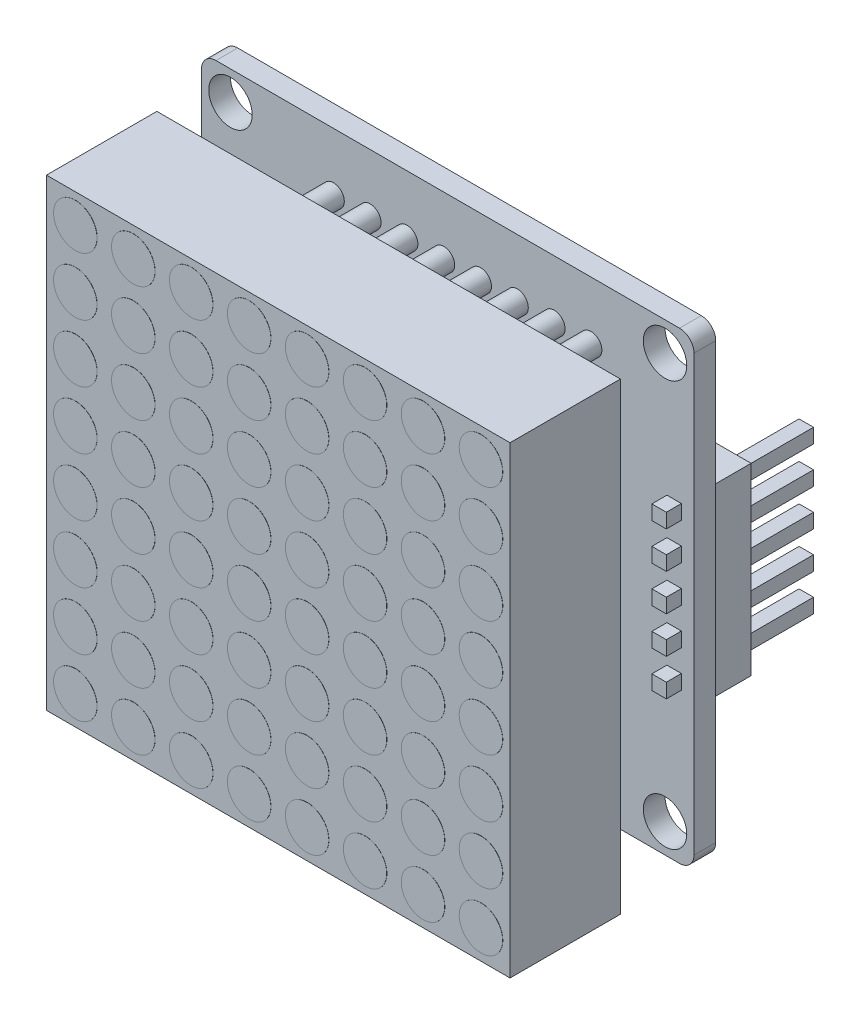
SolidWorks part; units mm, degrees
ref_plane "Alzado" through (0, 0, 0) normal (0, 0, 1) x (1, 0, 0)
ref_plane "Planta" through (0, 0, 0) normal (0, 1, 0) x (1, 0, 0)
ref_plane "Vista lateral" through (0, 0, 0) normal (1, 0, 0) x (0, 0, -1)
sketch "Croquis1" plane through (0, 0, 0) normal (0, 0, 1) x (1, 0, 0)
  line L0 (-22.5, 14) -> (7.5, 14) construction
  line L1 (-23.5, 16) -> (8.5, 16)
  line L2 (-24.5, 15) -> (-24.5, -15)
  line L3 (-23.5, -16) -> (8.5, -16)
  line L4 (9.5, 15) -> (9.5, -15)
  line L7 (-22.5, 14) -> (-22.5, -14) construction
  line L8 (-22.5, -14) -> (7.5, -14) construction
  line L9 (7.5, -14) -> (7.5, 14) construction
  arc A0 (-23.5, -16) -> (-24.5, -15) centre (-23.5, -15) cw
  arc A1 (-23.5, 16) -> (-24.5, 15) centre (-23.5, 15) ccw
  arc A2 (9.5, 15) -> (8.5, 16) centre (8.5, 15) ccw
  arc A3 (9.5, -15) -> (8.5, -16) centre (8.5, -15) cw
  circle A4 centre (-22.5, -14) radius 1.5
  circle A5 centre (-22.5, 14) radius 1.5
  circle A6 centre (7.5, 14) radius 1.5
  circle A7 centre (7.5, -14) radius 1.5
  point P0 (0, 0)
  dimension "D3" = 1
  dimension "D4" = 1
  dimension "D5" = 1
  dimension "D6" = 1
  dimension "D7" = 2
  dimension "D1" = 2
  dimension "D2" = 2
  dimension "D8" = 2
  dimension "D9" = 32
extrude "Saliente-Extruir1" add sketch "Croquis1" along normal blind 1.5
sketch "Croquis2" plane through (0, 0, 1.5) normal (0, 0, 1) x (1, 0, 0)
  line L0 (-24.5, 15) -> (-24.5, -15) construction
  line L1 (-24.4, -6.35) -> (-21.86, -6.35)
  line L2 (-24.4, -6.35) -> (-24.4, 6.35)
  line L3 (-24.4, 6.35) -> (-21.86, 6.35)
  line L4 (-21.86, -6.35) -> (-21.86, 6.35)
  line L5 (-21.86, 0) -> (-24.4, 0) construction
  line L6 (-23.5, -16) -> (8.5, -16) construction
  line L7 (-7.5, 16) -> (-7.5, -16) construction
  line L8 (8.5, 16) -> (-23.5, 16) construction
  line L9 (-24.4, -6.35) -> (-21.86, -6.35)
  line L10 (-24.4, 6.35) -> (-21.86, 6.35)
  line L11 (9.4, 6.35) -> (6.86, 6.35)
  line L12 (6.86, -6.35) -> (6.86, 6.35)
  line L13 (9.4, -6.35) -> (6.86, -6.35)
  line L14 (9.4, -6.35) -> (9.4, 6.35)
  dimension "D1" = 2.54
  dimension "D2" = 12.7
  dimension "D3" = 0.1
  dimension "D4" = 16
extrude "Saliente-Extruir2" add sketch "Croquis2" against normal blind 2.54 from surface contours L1 L4 L3 L2 | L13 L14 L11 L12 region at (-23.13, 0, 1.5) region at (8.13, 0, 1.5) starting at face at (9, 14, 0)
sketch "Croquis3" plane through (0, 0, 1.5) normal (0, 0, 1) x (1, 0, 0)
  line L0 (8.5, 16) -> (-23.5, 16) construction
  line L1 (-22.5, 16) -> (9.5, 16) construction
  line L2 (-22.5, 16) -> (-22.5, -16) construction
  line L3 (-22.5, -16) -> (9.5, -16) construction
  line L4 (9.5, 16) -> (9.5, -16) construction
  line L5 (9.5, -15) -> (9.5, 15) construction
  line L6 (-6.5, 16) -> (-6.5, -16) construction
  line L7 (-16.66, 12) -> (3.66, 12) construction
  line L12 (-16.66, 13.9501) -> (3.66, 13.9501) construction
  line L13 (-16.66, 13.9501) -> (-16.66, 10.0499) construction
  line L14 (-16.66, 10.0499) -> (3.66, 10.0499) construction
  line L15 (3.66, 13.9501) -> (3.66, 10.0499) construction
  line L16 (-22.5, 0) -> (-6.5, 0) construction
  line L17 (-6.5, 13.9501) -> (-6.5, 10.0499) construction
  circle A0 centre (-15.39, 12) radius 0.75
  circle A1 centre (-12.85, 12) radius 0.75
  circle A2 centre (-10.31, 12) radius 0.75
  circle A3 centre (-7.77, 12) radius 0.75
  circle A4 centre (-5.23, 12) radius 0.75
  circle A5 centre (-2.69, 12) radius 0.75
  circle A6 centre (-0.15, 12) radius 0.75
  circle A7 centre (2.39, 12) radius 0.75
  circle A8 centre (2.39, -12) radius 0.75
  circle A9 centre (-0.15, -12) radius 0.75
  circle A10 centre (-2.69, -12) radius 0.75
  circle A11 centre (-5.23, -12) radius 0.75
  circle A12 centre (-7.77, -12) radius 0.75
  circle A13 centre (-10.31, -12) radius 0.75
  circle A14 centre (-12.85, -12) radius 0.75
  circle A15 centre (-15.39, -12) radius 0.75
  dimension "D2" = 8
  dimension "D3" = 4
  dimension "D4" = 1.27
  dimension "D1" = 32
  dimension "D5" = 20.32
extrude "Saliente-Extruir3" add sketch "Croquis3" along normal mid plane 5.08
sketch "Croquis4" plane through (0, 0, 4.04) normal (0, 0, 1) x (1, 0, 0)
  line L0 (-16.66, 12) -> (3.66, 12) construction
  line L1 (-16.66, 13.2) -> (3.66, 13.2)
  line L2 (-16.66, 13.2) -> (-16.66, 10.8)
  line L3 (-16.66, 10.8) -> (3.66, 10.8)
  line L4 (3.66, 13.2) -> (3.66, 10.8)
  line L5 (-6.5, 13.2) -> (-6.5, 10.8) construction
  line L6 (9.5, -15) -> (9.5, 15) construction
  line L7 (8.5, 16) -> (-23.5, 16) construction
  line L8 (-6.5, 12) -> (-6.5, -12) construction
  line L9 (-6.5, 0) -> (18.66, 0) construction
  line L10 (3.66, -13.2) -> (3.66, -10.8)
  line L11 (-16.66, -10.8) -> (3.66, -10.8)
  line L12 (-16.66, -13.2) -> (-16.66, -10.8)
  line L13 (-16.66, -13.2) -> (3.66, -13.2)
  dimension "D1" = 20.32
  dimension "D2" = 2.4
  dimension "D3" = 16
  dimension "D4" = 4
  dimension "D5" = 24
extrude "Saliente-Extruir4" add sketch "Croquis4" along normal blind 2.54
sketch "Croquis5" plane through (0, 0, 6.58) normal (0, 0, 1) x (1, 0, 0)
  line L0 (-16.66, 12) -> (3.66, 12) construction
  line L1 (-16.66, 13.2) -> (-16.66, 10.8) construction
  line L2 (3.66, 10.8) -> (3.66, 13.2) construction
  line L3 (3.66, 12) -> (-6.5, 13.2) construction
  line L4 (3.66, 13.2) -> (-16.66, 13.2) construction
  line L5 (-6.5, 13.2) -> (-6.7835, 10.8) construction
  line L6 (-16.66, 10.8) -> (3.66, 10.8) construction
  line L7 (-16.66, 12) -> (-16.66, -12) construction
  line L8 (-16.66, -10.8) -> (-16.66, -13.2) construction
  line L9 (-16.66, 0) -> (17.39, 0) construction
  circle A0 centre (-15.39, 12) radius 0.5
  circle A1 centre (-12.85, 12) radius 0.5
  circle A2 centre (-10.31, 12) radius 0.5
  circle A3 centre (-7.77, 12) radius 0.5
  circle A4 centre (-5.23, 12) radius 0.5
  circle A5 centre (-2.69, 12) radius 0.5
  circle A6 centre (-0.15, 12) radius 0.5
  circle A7 centre (2.39, 12) radius 0.5
  circle A8 centre (2.39, -12) radius 0.5
  circle A9 centre (-0.15, -12) radius 0.5
  circle A10 centre (-2.69, -12) radius 0.5
  circle A11 centre (-5.23, -12) radius 0.5
  circle A12 centre (-7.77, -12) radius 0.5
  circle A13 centre (-10.31, -12) radius 0.5
  circle A14 centre (-12.85, -12) radius 0.5
  circle A15 centre (-15.39, -12) radius 0.5
  dimension "D1" = 1.27
  dimension "D2" = 8
extrude "Cortar-Extruir1" cut sketch "Croquis5" against normal blind 1.27
sketch "Croquis6" plane through (0, 0, -2.54) normal (0, 0, -1) x (-1, 0, 0)
  line L0 (22.63, 5.08) -> (23.63, 5.08) construction
  line L1 (23.63, 5.58) -> (22.63, 5.58)
  line L2 (23.63, 5.58) -> (23.63, 4.58)
  line L3 (23.63, 4.58) -> (22.63, 4.58)
  line L4 (22.63, 5.58) -> (22.63, 4.58)
  line L13 (-9.4, 0) -> (24.4, 0) construction
  line L14 (23.13, 5.58) -> (23.13, 4.58) construction
  line L15 (21.86, 6.35) -> (21.86, -6.35) construction
  line L16 (23.63, 2.04) -> (22.63, 2.04)
  line L17 (22.63, 3.04) -> (22.63, 2.04)
  line L18 (23.63, 3.04) -> (22.63, 3.04)
  line L19 (23.63, 3.04) -> (23.63, 2.04)
  line L20 (23.63, -0.5) -> (22.63, -0.5)
  line L21 (22.63, 0.5) -> (22.63, -0.5)
  line L22 (23.63, 0.5) -> (22.63, 0.5)
  line L23 (23.63, 0.5) -> (23.63, -0.5)
  line L24 (23.63, -3.04) -> (22.63, -3.04)
  line L25 (22.63, -2.04) -> (22.63, -3.04)
  line L26 (23.63, -2.04) -> (22.63, -2.04)
  line L27 (23.63, -2.04) -> (23.63, -3.04)
  line L28 (23.63, -5.58) -> (22.63, -5.58)
  line L29 (22.63, -4.58) -> (22.63, -5.58)
  line L30 (23.63, -4.58) -> (22.63, -4.58)
  line L31 (23.63, -4.58) -> (23.63, -5.58)
  line L32 (7.5, -1002.5152) -> (7.5, 48997.4848) construction
  line L33 (-8.13, 5.58) -> (-8.13, 4.58) construction
  line L34 (-9.4, 6.35) -> (-9.4, -6.35) construction
  line L35 (24.4, 6.35) -> (24.4, -6.35) construction
  line L36 (-7.63, 5.08) -> (-8.63, 5.08) construction
  line L37 (-8.63, -4.58) -> (-8.63, -5.58)
  line L38 (-8.63, -4.58) -> (-7.63, -4.58)
  line L39 (-7.63, -4.58) -> (-7.63, -5.58)
  line L40 (-8.63, -5.58) -> (-7.63, -5.58)
  line L41 (-8.63, -2.04) -> (-8.63, -3.04)
  line L42 (-8.63, -2.04) -> (-7.63, -2.04)
  line L43 (-7.63, -2.04) -> (-7.63, -3.04)
  line L44 (-8.63, -3.04) -> (-7.63, -3.04)
  line L45 (-8.63, 0.5) -> (-8.63, -0.5)
  line L46 (-8.63, 0.5) -> (-7.63, 0.5)
  line L47 (-7.63, 0.5) -> (-7.63, -0.5)
  line L48 (-8.63, -0.5) -> (-7.63, -0.5)
  line L49 (-8.63, 3.04) -> (-8.63, 2.04)
  line L50 (-8.63, 3.04) -> (-7.63, 3.04)
  line L51 (-7.63, 3.04) -> (-7.63, 2.04)
  line L52 (-8.63, 2.04) -> (-7.63, 2.04)
  line L53 (-7.63, 5.58) -> (-7.63, 4.58)
  line L54 (-8.63, 4.58) -> (-7.63, 4.58)
  line L55 (-8.63, 5.58) -> (-8.63, 4.58)
  line L56 (-8.63, 5.58) -> (-7.63, 5.58)
  dimension "D1" = 1
  dimension "D2" = 1
  dimension "D4" = 1.27
  dimension "D5" = 5
extrude "Saliente-Extruir6" add sketch "Croquis6" along normal blind 5.08 and the other way blind 5.08 from surface starting at face at (-23.13, 0, -2.54)
sketch "Croquis11" plane through (0, 0, 6.58) normal (0, 0, 1) x (1, 0, 0)
  line L0 (8.5, 16) -> (-23.5, 16) construction
  line L1 (-22.5, 16) -> (9.5, 16)
  line L2 (-22.5, 16) -> (-22.5, -16)
  line L3 (-22.5, -16) -> (9.5, -16)
  line L4 (9.5, 16) -> (9.5, -16)
  line L5 (9.5, -15) -> (9.5, 15) construction
  dimension "D1" = 32
  dimension "D2" = 32
extrude "Saliente-Extruir8" add sketch "Croquis11" along normal blind 7.62
sketch "Croquis18" plane through (0, 0, 14.2) normal (0, 0, 1) x (1, 0, 0)
  line L0 (-22.5, -16) -> (9.5, -16) construction
  line L1 (-22.5, 16) -> (-22.5, -16) construction
  circle A0 centre (-20.5, -14) radius 1.5
  circle A1 centre (-16.5, -14) radius 1.5
  circle A2 centre (-12.5, -14) radius 1.5
  circle A3 centre (-8.5, -14) radius 1.5
  circle A4 centre (-4.5, -14) radius 1.5
  circle A5 centre (-0.5, -14) radius 1.5
  circle A6 centre (3.5, -14) radius 1.5
  circle A7 centre (7.5, -14) radius 1.5
  circle A8 centre (-16.5, -10) radius 1.5
  circle A9 centre (-12.5, -10) radius 1.5
  circle A10 centre (-8.5, -10) radius 1.5
  circle A11 centre (-4.5, -10) radius 1.5
  circle A12 centre (-0.5, -10) radius 1.5
  circle A13 centre (3.5, -10) radius 1.5
  circle A14 centre (7.5, -10) radius 1.5
  circle A15 centre (-16.5, -6) radius 1.5
  circle A16 centre (-12.5, -6) radius 1.5
  circle A17 centre (-8.5, -6) radius 1.5
  circle A18 centre (-4.5, -6) radius 1.5
  circle A19 centre (-0.5, -6) radius 1.5
  circle A20 centre (3.5, -6) radius 1.5
  circle A21 centre (7.5, -6) radius 1.5
  circle A22 centre (-16.5, -2) radius 1.5
  circle A23 centre (-12.5, -2) radius 1.5
  circle A24 centre (-8.5, -2) radius 1.5
  circle A25 centre (-4.5, -2) radius 1.5
  circle A26 centre (-0.5, -2) radius 1.5
  circle A27 centre (3.5, -2) radius 1.5
  circle A28 centre (7.5, -2) radius 1.5
  circle A29 centre (-16.5, 2) radius 1.5
  circle A30 centre (-12.5, 2) radius 1.5
  circle A31 centre (-8.5, 2) radius 1.5
  circle A32 centre (-4.5, 2) radius 1.5
  circle A33 centre (-0.5, 2) radius 1.5
  circle A34 centre (3.5, 2) radius 1.5
  circle A35 centre (7.5, 2) radius 1.5
  circle A36 centre (-16.5, 6) radius 1.5
  circle A37 centre (-12.5, 6) radius 1.5
  circle A38 centre (-8.5, 6) radius 1.5
  circle A39 centre (-4.5, 6) radius 1.5
  circle A40 centre (-0.5, 6) radius 1.5
  circle A41 centre (3.5, 6) radius 1.5
  circle A42 centre (7.5, 6) radius 1.5
  circle A43 centre (-16.5, 10) radius 1.5
  circle A44 centre (-12.5, 10) radius 1.5
  circle A45 centre (-8.5, 10) radius 1.5
  circle A46 centre (-4.5, 10) radius 1.5
  circle A47 centre (-0.5, 10) radius 1.5
  circle A48 centre (3.5, 10) radius 1.5
  circle A49 centre (7.5, 10) radius 1.5
  circle A50 centre (-16.5, 14) radius 1.5
  circle A51 centre (-12.5, 14) radius 1.5
  circle A52 centre (-8.5, 14) radius 1.5
  circle A53 centre (-4.5, 14) radius 1.5
  circle A54 centre (-0.5, 14) radius 1.5
  circle A55 centre (3.5, 14) radius 1.5
  circle A56 centre (7.5, 14) radius 1.5
  circle A57 centre (-20.5, -10) radius 1.5
  circle A58 centre (-20.5, -6) radius 1.5
  circle A59 centre (-20.5, -2) radius 1.5
  circle A60 centre (-20.5, 2) radius 1.5
  circle A61 centre (-20.5, 6) radius 1.5
  circle A62 centre (-20.5, 10) radius 1.5
  circle A63 centre (-20.5, 14) radius 1.5
  dimension "D1" = 8
  dimension "D3" = 2
  dimension "D4" = 2
  dimension "D2" = 8
extrude "Saliente-Extruir9" add sketch "Croquis18" along normal blind 0.01
